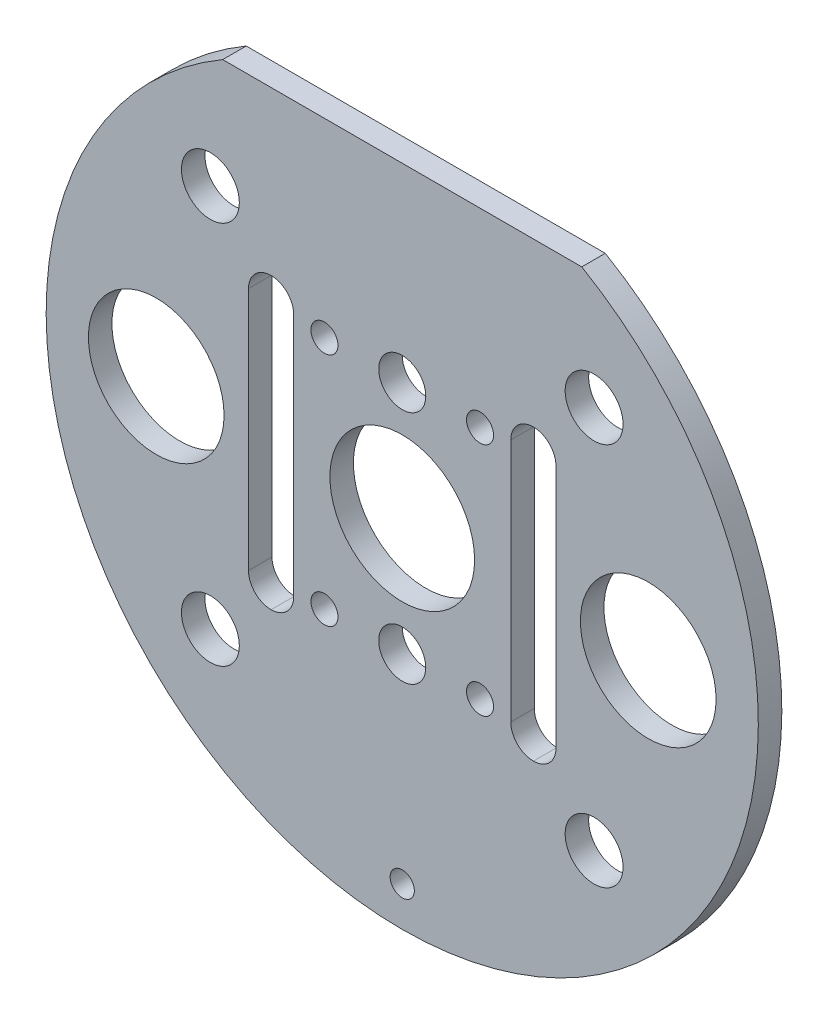
SolidWorks part; units mm, degrees
ref_plane "前视基准面" through (0, 0, 0) normal (0, 0, 1) x (1, 0, 0)
ref_plane "上视基准面" through (0, 0, 0) normal (0, 1, 0) x (1, 0, 0)
ref_plane "右视基准面" through (0, 0, 0) normal (1, 0, 0) x (0, 0, -1)
sketch "草图1" plane through (0, 0, 0) normal (0, 0, 1) x (1, 0, 0)
  circle A0 centre (0, 0) radius 50
  dimension "D1" = 100
extrude "凸台-拉伸1" add sketch "草图1" along normal blind 3.302
sketch "草图2" plane through (0, 0, 3.302) normal (0, 0, 1) x (1, 0, 0)
  line L0 (0, 0) -> (0, 69.5531) construction
  line L1 (0, 0) -> (-26.9408, 26.9408) construction
  line L2 (0, 0) -> (-31.0701, 0) construction
  line L3 (0, 0) -> (-26.9408, -26.9408) construction
  circle A0 centre (-26.9408, 26.9408) radius 4.064
  circle A1 centre (-26.9408, -26.9408) radius 4.064
  circle A2 centre (26.9408, -26.9408) radius 4.064
  circle A3 centre (26.9408, 26.9408) radius 4.064
  circle A4 centre (0, 0) radius 38.1 construction
  dimension "D1" = 8.128
  dimension "D2" = 45
  dimension "D3" = 76.2
  dimension "D4" = 8.128
  dimension "D5" = 45
extrude "切除-拉伸1" cut sketch "草图2" against normal through all
sketch "草图3" plane through (0, 0, 3.302) normal (0, 0, 1) x (1, 0, 0)
  line L0 (-25.2089, 43.18) -> (25.2089, 43.18)
  line L1 (25.2089, 43.18) -> (25.2089, 58.407)
  line L2 (25.2089, 58.407) -> (-25.2089, 58.407)
  line L3 (-25.2089, 58.407) -> (-25.2089, 43.18)
  circle A0 centre (0, 0) radius 50 construction
  dimension "D1" = 43.18
extrude "切除-拉伸2" cut sketch "草图3" against normal through all
sketch "草图4" plane through (0, 0, 3.302) normal (0, 0, 1) x (1, 0, 0)
  circle A0 centre (0, 0) radius 10.16
  dimension "D1" = 20.32
extrude "切除-拉伸3" cut sketch "草图4" against normal through all
sketch "草图6" plane through (0, 0, 3.302) normal (0, 0, 1) x (1, 0, 0)
  line L0 (0, 43.18) -> (0, -63.1689) construction
  line L1 (-25.2089, 43.18) -> (25.2089, 43.18) construction
  line L2 (-55.4747, 0) -> (58.1198, 0) construction
sketch "草图8" plane through (0, 0, 3.302) normal (0, 0, 1) x (1, 0, 0)
  line L0 (0, 43.18) -> (0, -63.1689) construction
  line L1 (15.24, 20.32) -> (21.59, 20.32)
  line L2 (15.24, 20.32) -> (15.24, -20.32)
  line L3 (15.24, -20.32) -> (21.59, -20.32)
  line L4 (21.59, 20.32) -> (21.59, -20.32)
  line L6 (-55.4747, 0) -> (58.1198, 0) construction
  line L7 (0, 0) -> (0, 55.0156) construction
  line L8 (-21.59, 20.32) -> (-21.59, -20.32)
  line L9 (-15.24, -20.32) -> (-21.59, -20.32)
  line L10 (-15.24, 20.32) -> (-15.24, -20.32)
  line L11 (-15.24, 20.32) -> (-21.59, 20.32)
  circle A0 centre (34.544, 0) radius 9.525
  circle A1 centre (-34.544, 0) radius 9.525
  dimension "D5" = 19.05
  dimension "D6" = 34.544
  dimension "D1" = 15.24
  dimension "D2" = 6.35
  dimension "D3" = 40.64
  dimension "D4" = 20.32
extrude "切除-拉伸4" cut sketch "草图8" against normal through all
sketch "草图9" plane through (0, 0, 3.302) normal (0, 0, 1) x (1, 0, 0)
  line L0 (0, 43.18) -> (0, -63.1689) construction
  line L2 (0, 38.6357) -> (0, -17.2565) construction
  line L3 (-24.6406, 0) -> (22.6594, 0) construction
  line L4 (-55.4747, 0) -> (58.1198, 0) construction
  circle A0 centre (-10.922, 16.51) radius 1.9
  circle A1 centre (10.922, 16.51) radius 1.9
  circle A2 centre (-10.922, -16.51) radius 1.9
  circle A3 centre (10.922, -16.51) radius 1.9
  circle A4 centre (0, 16.51) radius 3.302
  circle A5 centre (0, -16.51) radius 3.302
  dimension "D1" = 3.8
  dimension "D2" = 10.922
  dimension "D3" = 16.51
  dimension "D4" = 16.51
  dimension "D5" = 6.604
extrude "切除-拉伸5" cut sketch "草图9" against normal through all
fillet "Fillet1" radius 3.175 8 edges at (15.24, 20.32, 1.651) (21.59, 20.32, 1.651) (21.59, -20.32, 1.651) (15.24, -20.32, 1.651) (-15.24, -20.32, 1.651) (-21.59, -20.32, 1.651) (-15.24, 20.32, 1.651) (-21.59, 20.32, 1.651)
hole_wizard "M3 Clearance Hole1" positions "Sketch3" profile "Sketch4" hole size "M3" standard "ANSI Metric"
sketch "Sketch3" plane through (0, 0, 3.302) normal (0, 0, 1) x (1, 0, 0)
  line L2 (0, 43.18) -> (0, -63.1689) construction
  point P0 (0, -44.45)
  dimension "D2" = 44.45
sketch "Sketch4" plane through (0, -44.45, 3.302) normal (1, 0, 0) x (0, -1, 0)
  line L0 (0, 0) -> (0, 26.4215)
  line L1 (0, 26.4215) -> (1.7, 25.4)
  line L2 (1.7, 25.4) -> (1.7, 0)
  line L5 (1.7, 0) -> (0, 0)
  line L10 (0, 26.4215) -> (-1.7, 25.4) construction
  line L11 (0, -6.35) -> (0, 107.95) construction
  dimension "Hole Dia." = 3.4
  dimension "Hole Depth" = 25.4
  dimension "Drill Angle" = 118
